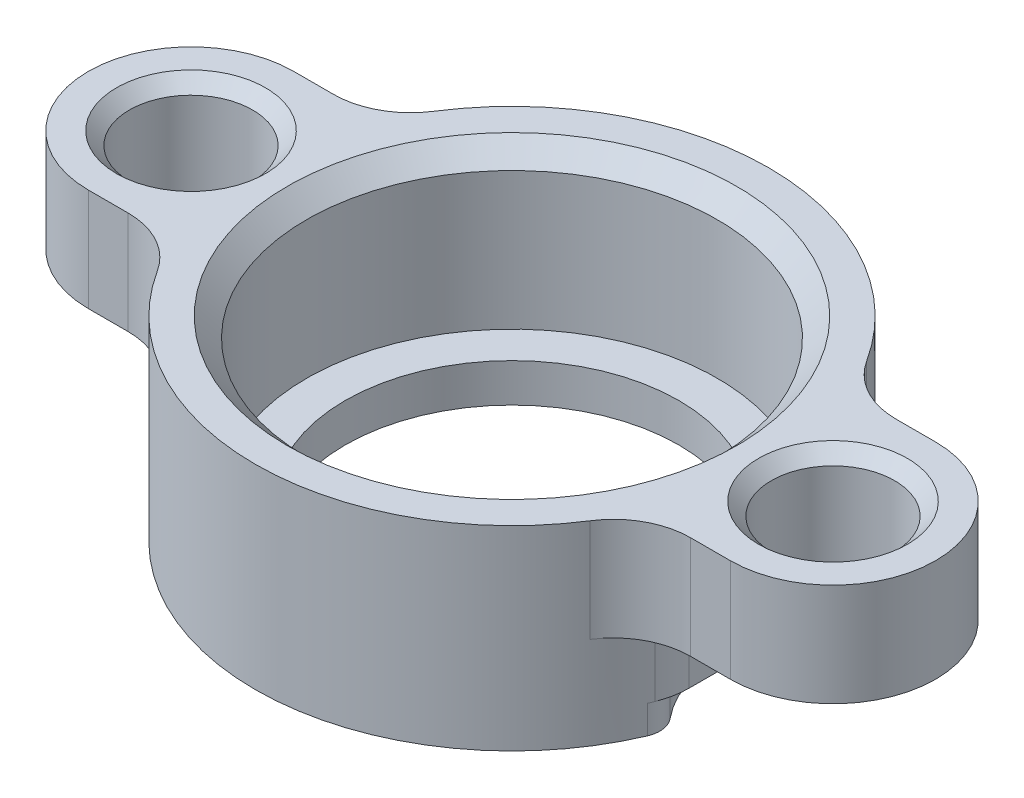
SolidWorks part; units mm, degrees
ref_plane "Plan de face" through (0, 0, 0) normal (0, 0, 1) x (1, 0, 0)
ref_plane "Plan de dessus" through (0, 0, 0) normal (0, 1, 0) x (1, 0, 0)
ref_plane "Plan de droite" through (0, 0, 0) normal (1, 0, 0) x (0, 0, -1)
sketch "Esquisse1" plane through (0, 0, 0) normal (0, 0, 1) x (1, 0, 0)
  line L0 (0, 6.6086) -> (0, -5.0424) construction
  line L1 (-6.5, -4) -> (-6.5, -5.5)
  line L2 (-6.5, -5.5) -> (-10, -5.5)
  line L3 (-10, -5.5) -> (-10, 2.1)
  line L4 (-10, 2.1) -> (-8, 2.1)
  line L9 (-8, 2.1) -> (-8, -4)
  line L10 (-8, -4) -> (-6.5, -4)
  point P5 (0, 0)
  point P9 (-8, 2.0335)
  point P10 (0, 0)
  dimension "D1" = 2
  dimension "D2" = 6.1
  dimension "D3" = 8
  dimension "D4" = 4
  dimension "D5" = 1.5
  dimension "D6" = 1.5
revolve "Révolution1" add sketch "Esquisse1" angle 360 about L0
sketch "Esquisse2" plane through (0, 2.1, 0) normal (0, 1, 0) x (1, 0, 0)
  line L0 (-12.5, -4) -> (-9.1652, -4)
  line L1 (-12.5, 4) -> (-9.1652, 4)
  line L2 (0, -4.18) -> (0, 4.18) construction
  line L5 (-9.5, -3.1225) -> (-9.5, 3.1225)
  circle A0 centre (-12.5, 0) radius 2.55 construction
  arc A1 (-12.5, 4) -> (-12.5, -4) centre (-12.5, 0) ccw
  circle A2 centre (0, 0) radius 10 construction
  arc A3 (-9.1652, 4) -> (-9.1652, -4) centre (0, 0) ccw
  circle A7 centre (-12.5, 0) radius 1.7 construction
  circle A9 centre (0, 0) radius 8 construction
  circle M6 centre (0, 0) radius 10
  dimension "D1" = 5.1
  dimension "D2" = 4
  dimension "D4" = 3.4
  dimension "D5" = 1.5
  dimension "D3" = 12.5
extrude "Boss.-Extru.1" add sketch "Esquisse2" against normal blind 4 contours L1 A1 L0 A0 M6 region at (-12.7463, 2.1, 0)
extrude "Enlèv. mat.-Extru.3" cut sketch "Esquisse2<6>" along normal up to surface (-4 mm away) from surface contours L5 M6 region at (-9.7004, 2.1, 0) up to face at (-12.0413, -1.9, 0) starting at face at (0, -5.5, 6.5)
sketch "Esquisse2<6>" plane through (0, 2.1, 0) normal (0, 1, 0) x (1, 0, 0) same geometry as "Esquisse2"
fillet "Congé2" radius 3 2 edges at (-9.5, -3.7, 3.1225) (-9.5, -3.7, -3.1225)
fillet "Congé3" radius 3 2 edges at (-9.1652, 0.1, -4) (-9.1652, 0.1, 4)
mirror "Symétrie1" about plane through (0, 0, 0) normal (1, 0, 0) of "Congé3", "Congé2", "Enlèv. mat.-Extru.3", "Boss.-Extru.1"
sketch "Esquisse8" plane through (0, 2.1, 0) normal (0, 1, 0) x (1, 0, 0)
  point P0 (-12.5, 0)
  point P3 (12.5, 0)
hole_wizard "Ø4.8 (4.8) Diameter Hole2" positions "Esquisse8" profile "Esquisse7" hole size "Ø4.8" standard "ANSI Metric"
sketch "Esquisse7" plane through (-12.5, 2.1, 0) normal (1, 0, 0) x (0, 0, 1)
  line L0 (0, 0) -> (0, 7.8421)
  line L1 (0, 7.8421) -> (2.4, 6.4)
  line L2 (2.4, 6.4) -> (2.4, 0)
  line L5 (2.4, 0) -> (0, 0)
  line L10 (0, 7.8421) -> (-2.4, 6.4) construction
  line L11 (0, -6.35) -> (0, 107.95) construction
  dimension "Hole Dia." = 4.8
  dimension "Hole Depth" = 6.4
  dimension "Drill Angle" = 118
chamfer "Chanfrein1" distance 0.5 angle 45 2 edges at (12.5, 2.1, 2.4) (-12.5, 2.1, 2.4)
sketch "Esquisse9" plane through (0, -5.5, 0) normal (0, -1, 0) x (1, 0, 0)
  circle A0 centre (-12.5, 0) radius 4.5
  circle A1 centre (12.5, 0) radius 4.5
  dimension "D1" = 9
extrude "Enlèv. mat.-Extru.4" cut sketch "Esquisse9" against normal blind 1.1
fillet "Congé4" radius 1 4 edges at (9.4211, -4.95, 3.2818) (9.4211, -4.95, -3.2818) (-9.4211, -4.95, 3.2818) (-9.4211, -4.95, -3.2818)
chamfer "Chanfrein2" distance 0.75 angle 45 1 edges at (0, 2.1, 8)
